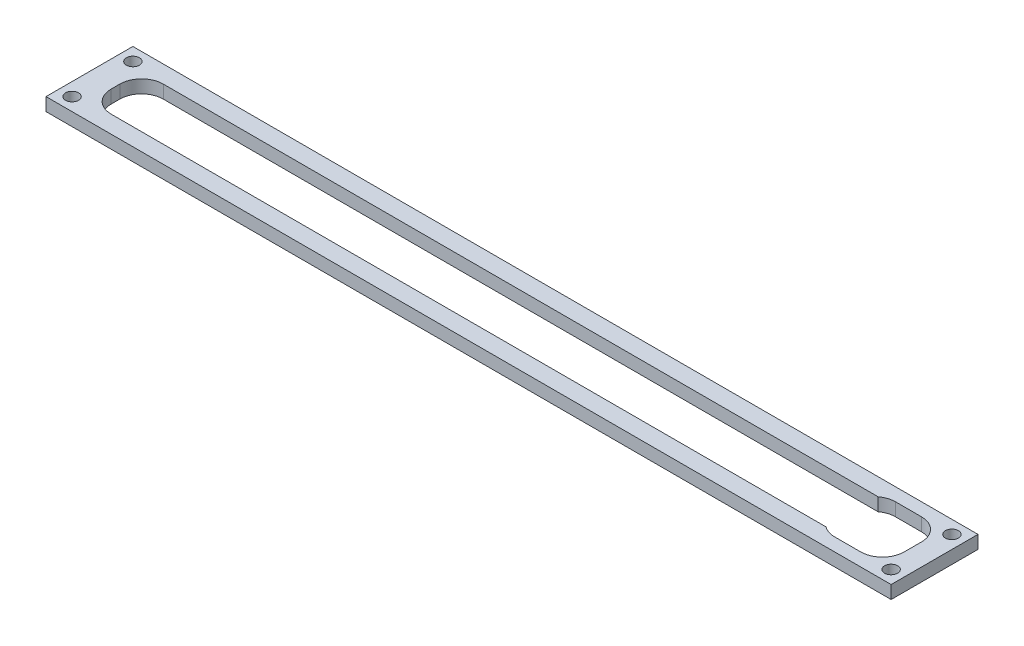
SolidWorks part; units mm, degrees
ref_plane "Front Plane" through (0, 0, 0) normal (0, 0, 1) x (1, 0, 0)
ref_plane "Top Plane" through (0, 0, 0) normal (0, 1, 0) x (1, 0, 0)
ref_plane "Right Plane" through (0, 0, 0) normal (1, 0, 0) x (0, 0, -1)
sketch "Sketch1" plane through (0, 0, 0) normal (0, 1, 0) x (1, 0, 0)
  line L0 (97.2958, 20) -> (97.2958, 0) construction
  line L1 (0, 0) -> (194.5917, 0)
  line L2 (0, 0) -> (0, 20)
  line L3 (0, 20) -> (194.5917, 20)
  line L4 (194.5917, 0) -> (194.5917, 20)
  line L5 (0, 10) -> (194.5917, 10) construction
  line L6 (97.2958, 16) -> (97.2958, 4) construction
  line L7 (6, 16) -> (188.5917, 16)
  line L8 (6, 16) -> (6, 4)
  line L9 (6, 4) -> (188.5917, 4)
  line L10 (188.5917, 16) -> (188.5917, 4)
  line L11 (6, 10) -> (188.5917, 10) construction
  circle A0 centre (3, 17) radius 1.5
  circle A1 centre (3, 3) radius 1.5
  circle A2 centre (191.5917, 3) radius 1.5
  circle A3 centre (191.5917, 17) radius 1.5
  point P17 (97.2958, 10)
  point P18 (97.2958, 10)
  dimension "D7" = 3
  dimension "D1" = 194.5917
  dimension "D2" = 20
  dimension "D3" = 182.5917
  dimension "D4" = 12
  dimension "D5" = 3
  dimension "D6" = 3
extrude "Boss-Extrude1" add sketch "Sketch1" along normal blind 3
sketch "Sketch2" plane through (0, 3, 0) normal (0, 1, 0) x (1, 0, 0)
  line L0 (92, 10) -> (-49908, 10) construction
  line L1 (188.5917, 4) -> (188.5917, 16) construction
  line L2 (175.5917, 17) -> (175.5917, 16)
  line L5 (188.5917, 16) -> (6, 16) construction
  line L6 (182.5917, 17) -> (182.5917, 3) construction
  line L7 (175.5917, 17) -> (189.5917, 17)
  line L9 (175.5917, 3) -> (189.5917, 3)
  line L10 (189.5917, 17) -> (189.5917, 3)
  line L12 (175.5917, 16) -> (188.5917, 16)
  line L13 (188.5917, 16) -> (188.5917, 4)
  line L14 (188.5917, 4) -> (175.5917, 4)
  line L15 (6, 4) -> (188.5917, 4) construction
  line L16 (175.5917, 4) -> (175.5917, 3)
  point P4 (188.5917, 10)
  point P23 (182.5917, 10)
  dimension "D1" = 1
  dimension "D2" = 14
  dimension "D3" = 14
extrude "Cut-Extrude1" cut sketch "Sketch2" against normal through all
fillet "Fillet1" radius 5 6 edges at (189.5917, 1.5, -17) (189.5917, 1.5, -3) (175.5917, 1.5, -17) (175.5917, 1.5, -3) (6, 1.5, -4) (6, 1.5, -16)
equation "\"TrackLength\"= ( ( \"n\" * 28 ) ) / cos ( \"MountAngle\" ) - ( 2 * \"x\" )"
equation "\"D1@Sketch1\"=\"TrackLength\""
equation "\"TrackWidth\"= \"MarbleTrackWidth\" + ( 2 * 4 )"
equation "\"D2@Sketch1\"=\"TrackWidth\""
equation "\"MarbleTrackWidth\"= \"MarbleWidth\" - 1"
equation "\"MarbleTrackLength\"= \"TrackLength\" - ( 2 * 6 )"
equation "\"D3@Sketch1\"=\"MarbleTrackLength\""
equation "\"D4@Sketch1\"=\"MarbleTrackWidth\""
equation "\"MarbleWidth\"= 13"
equation "\"n\"= 7"
equation "\"MountAngle\"= 10"
equation "\"x\"= 14 / cos ( \"MountAngle\" ) - 12"
